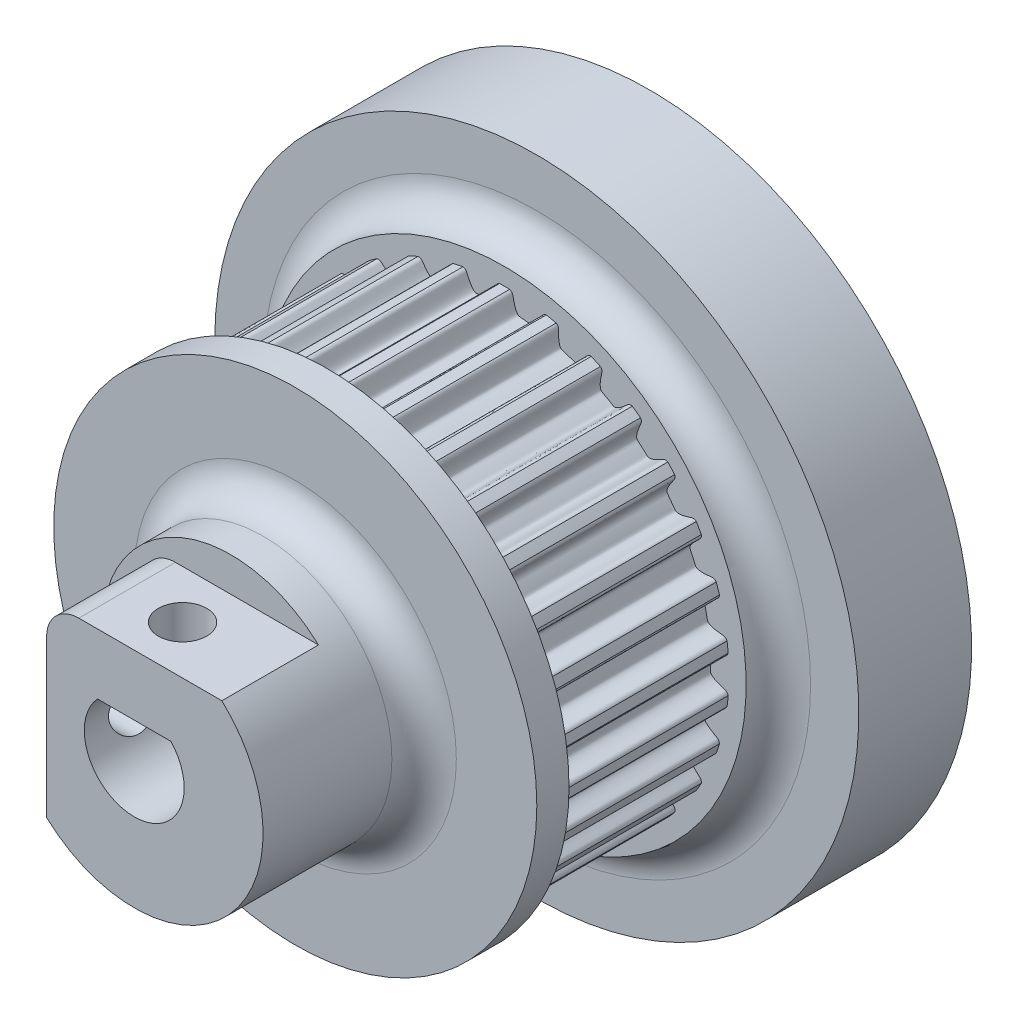
SolidWorks part; units mm, degrees
ref_plane "前视基准面" through (0, 0, 0) normal (0, 0, 1) x (1, 0, 0)
ref_plane "上视基准面" through (0, 0, 0) normal (0, 1, 0) x (1, 0, 0)
ref_plane "右视基准面" through (0, 0, 0) normal (1, 0, 0) x (0, 0, -1)
other "Configuration Table"
ref_axis "基准轴1" through (0, 0, 55) along (0, 0, -1)
sketch "SketchRevolveGearBelt01" plane through (0, 0, 0) normal (1, 0, 0) x (0, 0, -1)
  line L0 (0, 0) -> (1, 0) construction
  line L1 (9.774, 0) -> (9.774, 11.9239)
  line L2 (9.774, 11.9239) -> (9.012, 11.9239)
  line L3 (9.012, 11.9239) -> (9.012, 14.1724)
  line L4 (9.012, 14.1724) -> (9.48, 15.3023)
  line L5 (9.48, 15.3023) -> (8.7761, 15.5939)
  line L6 (8.7761, 15.5939) -> (8.25, 14.3239)
  line L7 (8.25, 14.3239) -> (8.25, 13.929)
  line L8 (8.25, 13.929) -> (-8.25, 13.929)
  line L9 (-8.25, 13.929) -> (-8.25, 14.3239)
  line L10 (-8.25, 14.3239) -> (-8.7761, 15.5939)
  line L11 (-8.7761, 15.5939) -> (-9.48, 15.3023)
  line L12 (-9.48, 15.3023) -> (-9.012, 14.1724)
  line L13 (-9.012, 14.1724) -> (-9.012, 11.9239)
  line L14 (-9.012, 11.9239) -> (-9.774, 11.9239)
  line L15 (-9.774, 11.9239) -> (-9.774, 0)
  line L16 (-9.774, 0) -> (9.774, 0)
  dimension "GearBeltFlange1OutsideLength" = 2.2484
  dimension "GearBeltFlange1X" = 0.468
  dimension "GearBeltFlange1Y" = 1.13
  dimension "GearBeltFlangeThickness" = 0.762
  dimension "GearBeltFlangeInside" = 0.395
  dimension "GearBeltOutsideDiameter" = 13.929
  dimension "GearBeltFlange2X" = 0.468
revolve "Gates_PowerGrip_GT_3mm, 15mm Belt Width" add sketch "SketchRevolveGearBelt01" angle 360 about L0
sketch "SketchToothGearBelt01" plane through (0, 0, 0) normal (0, 0, 1) x (1, 0, 0)
  arc A0 (13.8891, 1.2181) -> (13.8891, -1.2181) centre (0, 0) cw
  spline S0 degree 3 poles (13.8891, -1.2181) (13.8898, -1.1984) (13.8877, -1.1687) (13.8793, -1.13) (13.8701, -1.1018) (13.8581, -1.0746) (13.8436, -1.0487) (13.8265, -1.0244) (13.8072, -1.0019) (13.7857, -0.9814) (13.7623, -0.9631) (13.7372, -0.9473) (13.7107, -0.9338) (13.6451, -0.91) (13.5609, -0.8839) (13.4609, -0.8512) (13.3848, -0.8247) (13.3132, -0.7983) (13.2463, -0.7718) (13.184, -0.7454) (13.1262, -0.7189) (13.0731, -0.6924) (13.0246, -0.666) (12.9807, -0.6395) (12.9413, -0.6131) (12.9066, -0.5866) (12.8764, -0.5602) (12.8508, -0.5336) (12.8298, -0.5071) (12.8134, -0.4805) (12.8017, -0.4537) (12.7944, -0.4269) (12.7911, -0.3754) (12.7968, -0.3) (12.7974, -0.1999) (12.7989, -0.1) (12.7992, 0) (12.7989, 0.1) (12.7974, 0.1999) (12.7968, 0.3) (12.7911, 0.3754) (12.7944, 0.4269) (12.8017, 0.4537) (12.8134, 0.4805) (12.8298, 0.5071) (12.8508, 0.5336) (12.8764, 0.5602) (12.9066, 0.5866) (12.9413, 0.6131) (12.9807, 0.6395) (13.0246, 0.666) (13.0731, 0.6924) (13.1262, 0.7189) (13.184, 0.7454) (13.2463, 0.7718) (13.3132, 0.7983) (13.3848, 0.8247) (13.4609, 0.8512) (13.5609, 0.8839) (13.6451, 0.91) (13.7107, 0.9338) (13.7372, 0.9473) (13.7623, 0.9631) (13.7857, 0.9814) (13.8072, 1.0019) (13.8265, 1.0244) (13.8436, 1.0487) (13.8581, 1.0746) (13.8701, 1.1018) (13.8793, 1.13) (13.8877, 1.1687) (13.8898, 1.1984) (13.8891, 1.2181) knots 0 0 0 0 0.015924 0.023886 0.031848 0.03981 0.047771 0.055733 0.063695 0.071657 0.079619 0.087581 0.095543 0.103505 0.143783 0.166612 0.188267 0.208755 0.228086 0.24627 0.26332 0.279253 0.294087 0.307847 0.320562 0.332271 0.343022 0.352878 0.361922 0.370259 0.378023 0.385381 0.392526 0.419433 0.446289 0.473144 0.5 0.526856 0.553711 0.580567 0.607474 0.614619 0.621977 0.629741 0.638078 0.647122 0.656978 0.667729 0.679438 0.692153 0.705913 0.720747 0.73668 0.75373 0.771914 0.791245 0.811733 0.833388 0.856217 0.896495 0.904457 0.912419 0.920381 0.928343 0.936305 0.944267 0.952229 0.96019 0.968152 0.976114 0.984076 1 1 1 1
extrude "ToothExtrudeCutGearBelt01" cut sketch "SketchToothGearBelt01" against normal blind 8.25 and the other way blind 8.25
pattern_circular "Tooth Pattern, 30" count 30 every 12 about axis through (0, 0, 55) along (0, 0, -1) of "ToothExtrudeCutGearBelt01"
sketch "BoreRevolveSketch" plane through (0, 0, 0) normal (1, 0, 0) x (0, 0, -1)
  line L0 (0, 0) -> (1, 0) construction
  line L1 (-9.774, 0) -> (9.774, 0)
  line L2 (9.774, 0) -> (9.774, 5)
  line L3 (9.774, 5) -> (-9.774, 5)
  line L4 (-9.774, 5) -> (-9.774, 0)
  dimension "TaperSide1" = 5
  dimension "TaperSide2" = 5
revolve "BoreRevolveCut" cut sketch "BoreRevolveSketch" angle 360 about L0
sketch "AuxiliarySketchGearBelt01" plane through (0, 0, 0) normal (0, 0, 1) x (1, 0, 0)
  circle A0 centre (0, 0) radius 14.3239 construction
  dimension "PitchDiameter" = 28.6479
sketch "草图5" plane through (0, 0, 9.774) normal (0, 0, 1) x (1, 0, 0)
  circle A0 centre (0, 0) radius 18.2681
extrude "切除-拉伸2" cut sketch "草图5" against normal blind 4.55
sketch "草图7" plane through (0, 0, -9.774) normal (0, 0, -1) x (-1, 0, 0)
  circle A0 centre (0, 0) radius 17.2171
extrude "切除-拉伸3" cut sketch "草图7" against normal blind 4
sketch "草图8" plane through (0, 0, -5.774) normal (0, 0, -1) x (-1, 0, 0)
  circle A0 centre (0, 0) radius 15
  dimension "D1" = 30
extrude "凸台-拉伸1" add sketch "草图8" along normal blind 2
sketch "草图9" plane through (0, 0, 5.224) normal (0, 0, 1) x (1, 0, 0)
  circle A0 centre (0, 0) radius 15
extrude "凸台-拉伸2" add sketch "草图9" along normal blind 2
sketch "草图10" plane through (0, 0, -7.774) normal (0, 0, -1) x (-1, 0, 0)
  circle A0 centre (0, 0) radius 5
  dimension "D1" = 10
extrude "切除-拉伸4" cut sketch "草图10" against normal through all
sketch "草图11" plane through (0, 0, 7.224) normal (0, 0, 1) x (1, 0, 0)
  circle A0 centre (0, 0) radius 3
  circle A1 centre (0, 0) radius 8
  dimension "D1" = 6
  dimension "D2" = 16
extrude "凸台-拉伸3" add sketch "草图11" along normal blind 10
fillet "圆角1" radius 2 1 edges at (8, 0, 7.224)
sketch "草图13" plane through (0, 0, -7.774) normal (0, 0, -1) x (-1, 0, 0)
  circle A0 centre (0, 0) radius 5
  circle A1 centre (0, 0) radius 20
  dimension "D1" = 40
sketch "草图14" plane through (0, 0, 17.224) normal (0, 0, 1) x (1, 0, 0)
  line L0 (0, 0) -> (0, 2.1)
  line L1 (-1000, 2.1) -> (49000, 2.1) construction
  circle A0 centre (0, 0) radius 3.1
  circle M4 centre (0, 0) radius 3
  dimension "D1" = 6.2
  dimension "D2" = 2.1
extrude "切除-拉伸5" cut sketch "草图14" against normal through all contours L1 A0 M4 | A0 L1 M4 region at (0, 3.0533, 17.224) region at (-2.2114, 2.0919, 17.224)
sketch "草图15" plane through (0, 0, 17.224) normal (0, 0, 1) x (1, 0, 0)
  line L0 (0, 0) -> (0, 2.1)
  line L1 (-1000.0961, 2.1) -> (48999.9039, 2.1)
  circle A0 centre (0, 0) radius 3.1
  circle M2 centre (0, 0) radius 3.1
extrude "凸台-拉伸5" add sketch "草图15" against normal blind 10 contours L1 M2 region at (0, 2.5061, 17.224)
sketch "草图16" plane through (0, 0, 17.224) normal (0, 0, 1) x (1, 0, 0)
  line L1 (-5.4416, -5.8643) -> (5.4416, -5.8643)
  line L2 (-5.4416, -5.8643) -> (-5.4416, 5.8643)
  line L3 (-5.4416, 5.8643) -> (5.4416, 5.8643)
  line L4 (5.4416, -5.8643) -> (5.4416, 5.8643)
  line L5 (-5.4416, -5.8643) -> (5.4416, 5.8643) construction
  line L6 (-5.4416, 5.8643) -> (5.4416, -5.8643) construction
  circle A0 centre (0, 0) radius 8 construction
  circle A1 centre (0, 0) radius 8
  point P0 (0, 0)
  circle M3 centre (0, 0) radius 8
extrude "切除-拉伸6" cut sketch "草图16" against normal blind 6 contours L3 M3 | L2 M3 region at (-6.4804, 0, 17.224) region at (0, 6.7291, 17.224)
fillet "圆角3" radius 2 1 edges at (-5.4416, 5.8643, 14.224)
sketch "草图17" plane through (0, 5.8643, 0) normal (0, 1, 0) x (1, 0, 0)
  line L0 (0, -17.224) -> (0, -14.224)
  line L1 (-3.1, -17.224) -> (3.1, -17.224) construction
  line L2 (0, -55) -> (0, 55) construction
  circle A0 centre (0, -14.224) radius 1.5
  dimension "D2" = 3
  dimension "D1" = 3
sketch "草图18" plane through (-5.4416, 0, 0) normal (-1, 0, 0) x (0, 0, 1)
  line L0 (55, 0) -> (-55, 0) construction
  line L1 (17.224, 0) -> (17.224, 2.1) construction
  circle A0 centre (14.224, 0) radius 1.5
  dimension "D1" = 3
  dimension "D2" = 3
extrude "凸台-拉伸8" add sketch "草图13" along normal blind 7
fillet "圆角4" radius 2 1 edges at (-15, 0, -7.774)
sketch "草图21" plane through (0, 0, -14.774) normal (0, 0, -1) x (-1, 0, 0)
  circle A0 centre (0, 0) radius 12
  circle A1 centre (0, 12) radius 2.4
  circle A2 centre (12, 0) radius 2.4
  circle A3 centre (0, -12) radius 2.4
  circle A4 centre (-12, 0) radius 2.4
  point P14 (0, 0)
  dimension "D1" = 24
  dimension "D2" = 4.8
  dimension "D3" = 4
extrude "切除-拉伸10" cut sketch "草图21" against normal blind 7 contours A1 | A4 | A2 | A3
sketch "草图22" plane through (0, 0, -14.774) normal (0, 0, -1) x (-1, 0, 0)
  circle A0 centre (0, 0) radius 5.25
  dimension "D1" = 10.5
extrude "切除-拉伸12" cut sketch "草图22" against normal blind 20
fillet "圆角5" radius 0.5 1 edges at (-5.25, 0, 5.226)
extrude "切除-拉伸13" cut sketch "草图17" against normal up to next contours A0 region at (1.0307, 5.8643, 15.2547)
extrude "切除-拉伸14" cut sketch "草图18" against normal up to next
